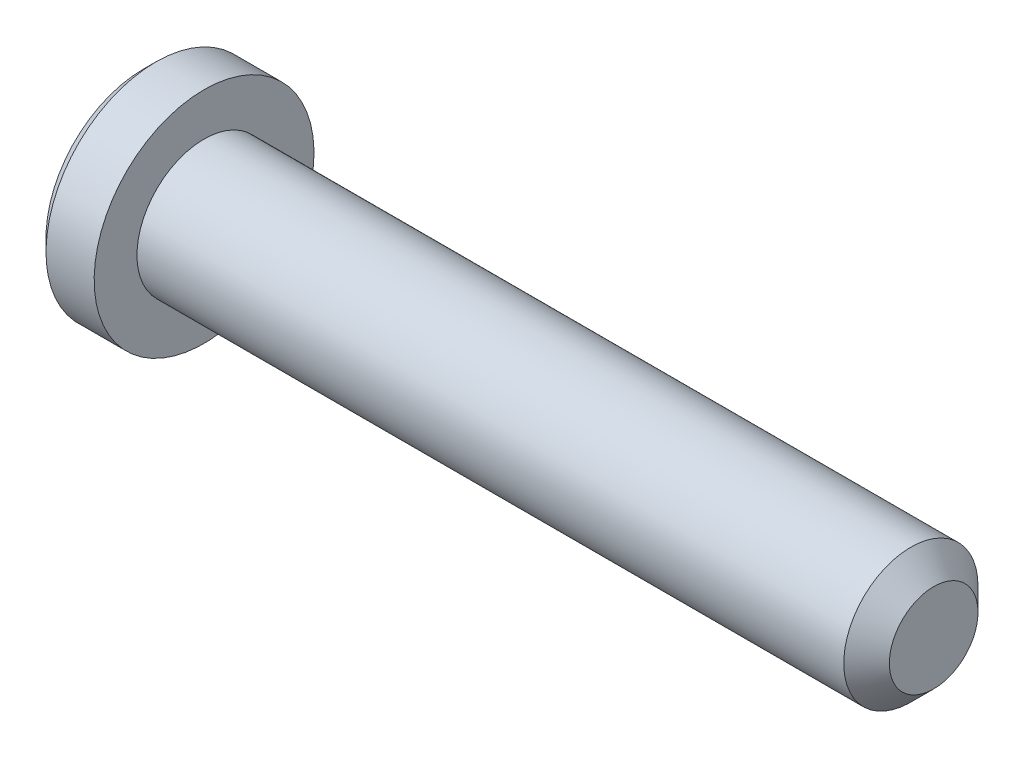
SolidWorks part; units mm, degrees
ref_plane "Front Plane" through (0, 0, 0) normal (0, 0, 1) x (1, 0, 0)
ref_plane "Top Plane" through (0, 0, 0) normal (0, 1, 0) x (1, 0, 0)
ref_plane "Right Plane" through (0, 0, 0) normal (1, 0, 0) x (0, 0, -1)
sketch "Sketch1" plane through (0, 0, 0) normal (0, 0, 1) x (1, 0, 0)
  line L0 (9.525, 0) -> (-9.525, 0) construction
  line L1 (9.525, 1.7526) -> (9.525, -1.7526) construction
  line L2 (-9.525, 2.8702) -> (-9.525, -2.8702) construction
  line L3 (-9.525, 2.8702) -> (-10.7823, 2.8702) construction
  line L4 (-10.7823, 2.8702) -> (-11.1125, 2.54) construction
  line L5 (-11.1125, 2.54) -> (-11.1125, -2.54) construction
  line L6 (-11.1125, -2.54) -> (-10.7823, -2.8702) construction
  line L7 (-10.7823, -2.8702) -> (-9.525, -2.8702) construction
  point P7 (-9.8425, 0)
  point P12 (6.35, -1.7526)
  dimension "D1" = 45
  dimension "Dec." = 3.5052
  dimension "Length" = 19.05
  dimension "Head Dia" = 5.7404
  dimension "Head Height" = 1.5875
  dimension "Hex Depth" = 1.27
  dimension "Chamfer" = 0.3302
  dimension "D2" = 3.175
ref_plane "Plane1" through (9.525, 0, 0) normal (1, 0, 0) x (0, 0, -1)
ref_plane "Plane2" through (-11.1125, 0, 0) normal (1, 0, 0) x (0, 0, -1)
sketch "Sketch2" plane through (9.525, 0, 0) normal (1, 0, 0) x (0, 0, -1)
  circle A0 centre (0, 0) radius 1.7526
extrude "Boss-Extrude1" add sketch "Sketch2" against normal up to vertex (19.05 mm away) up to point (-9.525, 0, 0)
sketch "Sketch3" plane through (9.525, 0, 0) normal (1, 0, 0) x (0, 0, -1)
  circle A0 centre (0, 0) radius 1.7526 construction
  circle A1 centre (0, 0) radius 1.7526
curve "Helix/Spiral1" [suppressed] pitch 0.7937 height 19.8438 turns 25 parameters "Pitch"=0.7937
chamfer "Chamfer1" distance 0.5953 angle 45 1 edges at (9.525, 0, -1.7526)
sketch "Sketch5" plane through (0, 0, 0) normal (0, 0, 1) x (1, 0, 0)
  line L0 (9.1777, 1.7526) -> (9.8723, 1.7526)
  line L1 (9.8723, 1.7526) -> (9.5746, 1.237)
  line L2 (9.5746, 1.237) -> (9.4754, 1.237)
  line L3 (9.4754, 1.237) -> (9.1777, 1.7526)
  line L4 (9.525, 1.237) -> (9.525, 1.7526) construction
  line L5 (9.3266, 1.4948) -> (9.7234, 1.4948) construction
  dimension "D1" = 60
  dimension "D2" = 0.3969
  dimension "D3" = 0.0992
sweep "Cut-Sweep1" [suppressed] cut profiles "Sketch5" path "Helix/Spiral1"
sketch "Sketch4" plane through (-11.1125, 0, 0) normal (1, 0, 0) x (0, 0, -1)
  line L0 (-2.8702, 0.7937) -> (2.8702, 0.7937) construction
  line L1 (0, 0.9165) -> (-0.7937, 0.4583)
  line L2 (-0.7937, 0.4583) -> (-0.7937, -0.4583)
  line L3 (-0.7937, -0.4583) -> (0, -0.9165)
  line L4 (0, -0.9165) -> (0.7937, -0.4583)
  line L5 (0.7937, -0.4583) -> (0.7937, 0.4583)
  line L6 (0.7937, 0.4583) -> (0, 0.9165)
  line L7 (0, 0) -> (0, 0.7937) construction
  circle A0 centre (0, 0) radius 0.7937 construction
  dimension "Hex Size" = 1.5875
  dimension "D1" = 5.7404
  dimension "D2" = 0.7937
sketch "Sketch6" plane through (0, 0, 0) normal (0, 0, 1) x (1, 0, 0)
  line L0 (-10.7823, 2.8702) -> (-11.1125, 2.54) construction
  line L1 (-9.525, 2.8702) -> (-10.7823, 2.8702) construction
  line L2 (-9.525, 2.8702) -> (-9.525, -2.8702) construction
  line L3 (-11.1125, 2.54) -> (-11.1125, -2.54) construction
  line L4 (-10.7823, 2.8702) -> (-11.1125, 2.54)
  line L5 (-9.525, 2.8702) -> (-10.7823, 2.8702)
  line L6 (-9.525, 2.8702) -> (-9.525, 0)
  line L7 (-11.1125, 2.54) -> (-11.1125, 0)
  line L8 (-9.525, 0) -> (-11.1125, 0) construction
  line L9 (-9.525, 0) -> (-11.1125, 0)
revolve "Revolve1" add sketch "Sketch6" angle 360 about L8
extrude "Cut-Extrude1" cut sketch "Sketch4" along normal up to vertex (1.27 mm away) up to point (-9.8425, 0, 0)
sketch "Sketch8" plane through (-11.1125, 0, 0) normal (-1, 0, 0) x (0, 0, 1)
  circle A1 centre (0, 0) radius 0.9165
extrude "Cut-Extrude2" cut sketch "Sketch8" against normal through all draft 45
equation "\"D3@Helix/Spiral1\" = \"Length@Sketch1\"+\"Pitch@Helix/Spiral1\""
equation "\"D3@Sketch5\" = \"Pitch@Helix/Spiral1\"*.125"
equation "\"D2@Sketch5\" = \"Pitch@Helix/Spiral1\"*.50"
equation "\"D1@Chamfer1\" = \"Pitch@Helix/Spiral1\"*.75"
equation "\"D2@Sketch1\" = \"Pitch@Helix/Spiral1\"*4"
equation "\"D1@Sketch4\" = \"Head Dia@Sketch1\""
